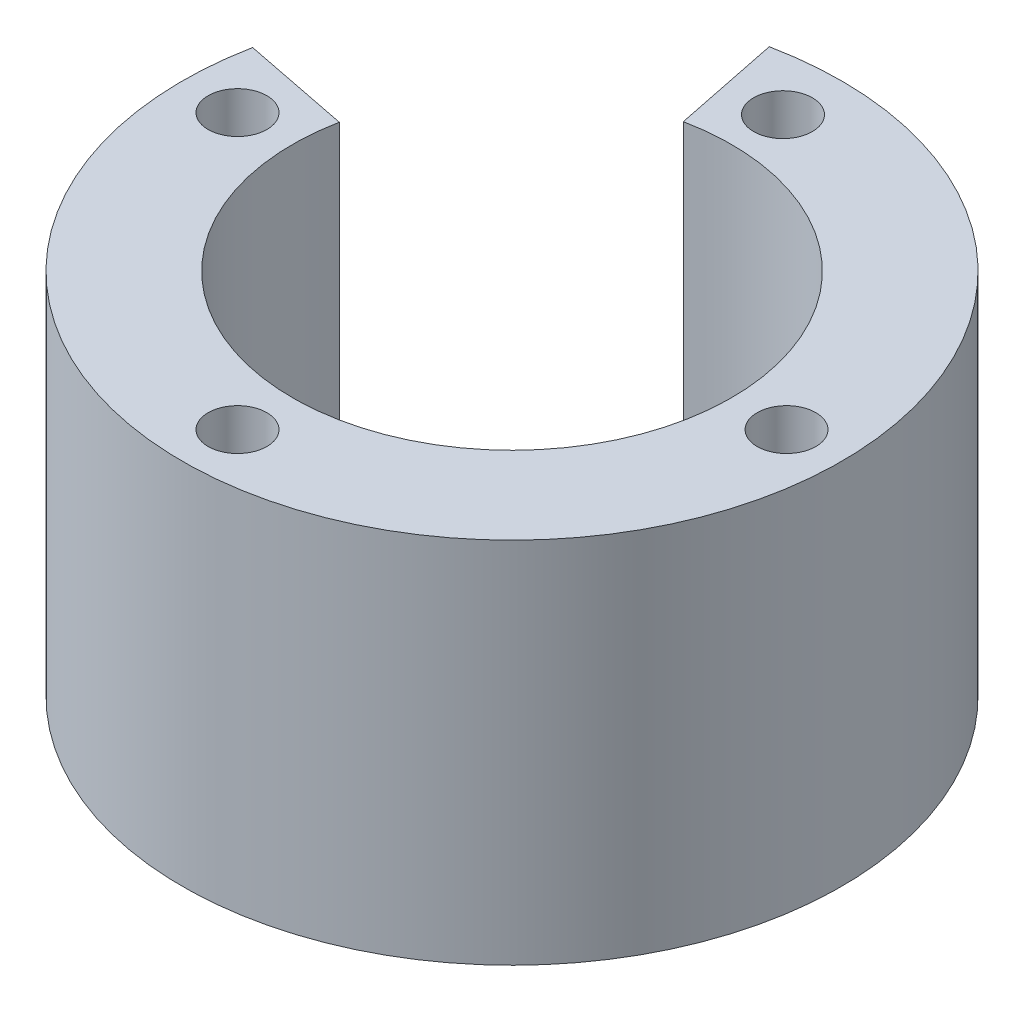
SolidWorks part; units mm, degrees
ref_plane "Front Plane" through (0, 0, 0) normal (0, 0, 1) x (1, 0, 0)
ref_plane "Top Plane" through (0, 0, 0) normal (0, 1, 0) x (1, 0, 0)
ref_plane "Right Plane" through (0, 0, 0) normal (1, 0, 0) x (0, 0, -1)
sketch "Sketch1" plane through (0, 0, 0) normal (0, 1, 0) x (1, 0, 0)
  line L15 (0, 0) -> (-3.5819, 17.6016)
  line L16 (0, 0) -> (-17.6213, 3.4837)
  circle A1 centre (-14.9624, 0) radius 1.6
  circle A2 centre (0, 14.7683) radius 1.6
  circle A3 centre (14.9624, 0) radius 1.6
  circle A4 centre (0, -14.9624) radius 1.6
  circle A5 centre (0, 0) radius 17.9624
  circle A6 centre (0, 0) radius 11.9624
  dimension "D1" = 3.2
  dimension "D2" = 23.9247
  dimension "D3" = 35.9247
  dimension "D4" = 14.9624
  dimension "D5" = 3.5819
  dimension "D6" = 14.9624
  dimension "D7" = 17.6213
  dimension "D8" = 14.7683
  dimension "D9" = 14.9624
extrude "Boss-Extrude1" add sketch "Sketch1" along normal blind 20.066 contours A6 L16 A5 L15 A1 A2 A3 A4 region at (-2.4858, 0, -14.7632)
sketch "Sketch2" plane through (0, 0, 0) normal (0, -1, 0) x (-1, 0, 0)
  line L0 (0, 0) -> (0, -11.9624)
  line L1 (0, -11.9624) -> (0, 11.9624)
  arc A0 (2.3854, 11.7221) -> (11.7352, 2.3201) centre (0, 0) ccw construction
